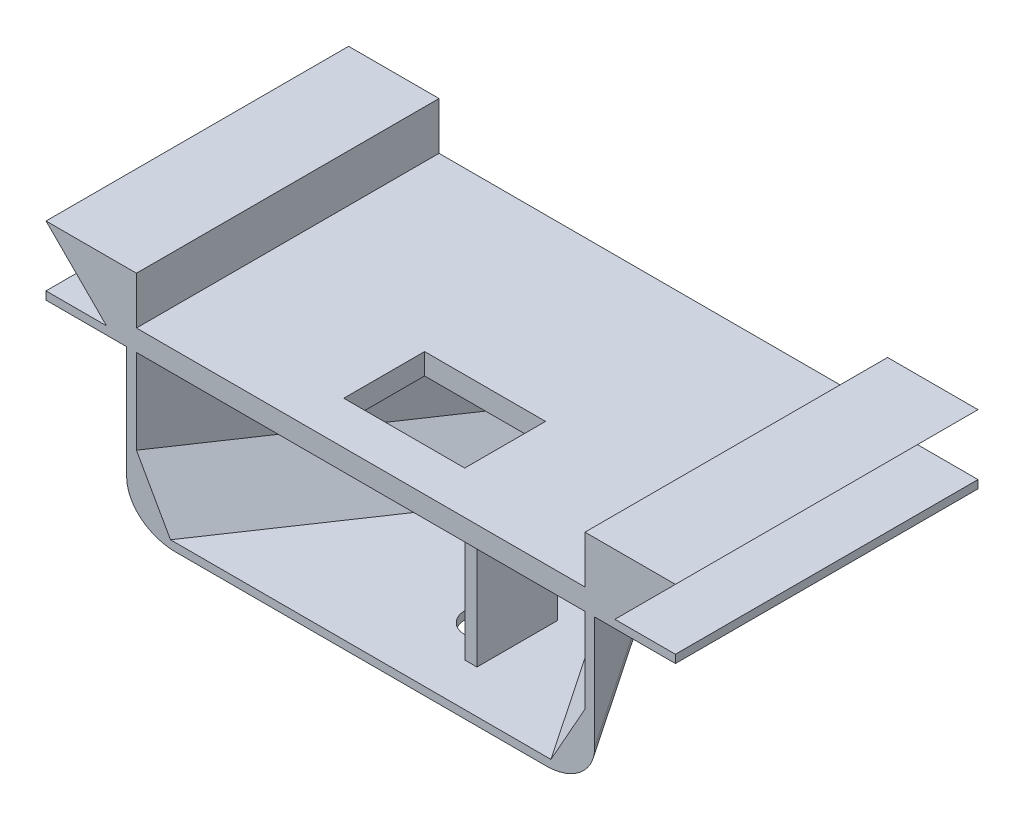
SolidWorks part; units mm, degrees
other "Camera1"
ref_plane "Front Plane" through (0, 0, 0) normal (0, 0, 1) x (1, 0, 0)
ref_plane "Top Plane" through (0, 0, 0) normal (0, 1, 0) x (1, 0, 0)
ref_plane "Right Plane" through (0, 0, 0) normal (1, 0, 0) x (0, 0, -1)
sketch "Sketch1" plane through (0, 0, 0) normal (0, 1, 0) x (1, 0, 0)
  line L0 (0, 0) -> (-116, 0)
  line L1 (-116, 0) -> (-75.5008, 60)
  line L2 (-75.5008, 60) -> (-40.5008, 60)
  line L3 (-40.5008, 60) -> (0, 0)
  dimension "D1" = 60
  dimension "D2" = 116
  dimension "D3" = 35
  dimension "D5" = 72.39
  dimension "D6" = 72.3891
extrude "Boss-Extrude1" add sketch "Sketch1" against normal blind 40
shell "Shell1" thickness 2 removed face at (-58, -20, 0)
sketch "Sketch5" plane through (0, 0, -58) normal (0, 0, 1) x (1, 0, 0)
  line L0 (-41.5637, -2) -> (-74.4378, -2) construction
  line L1 (-53.4928, -23) -> (-61.9928, -23)
  line L2 (-53.4928, -23) -> (-53.4928, -14.5)
  line L3 (-53.4928, -14.5) -> (-61.9928, -14.5)
  line L4 (-61.9928, -23) -> (-61.9928, -14.5)
  line L5 (-74.4378, -38) -> (-74.4378, -2) construction
  line L7 (-41.5637, -38) -> (-41.5637, -2) construction
  dimension "D1" = 12.445
  dimension "D2" = 8.5
  dimension "D3" = 12.5
  dimension "D4" = 11.929
extrude "Cut-Extrude5" cut sketch "Sketch5" against normal blind 6
chamfer "Chamfer3" distance 15 angle 25 2 edges at (-94.0124, -38, -29) (-21.9884, -38, -29) first distance on face at (-94.0124, -20, -29) first distance on face at (-21.9884, -20, -29)
fillet "Fillet1" radius 10 2 edges at (-20.2504, -40, -30) (-95.7504, -40, -30)
fillet "Fillet2" radius 5 5 edges at (-40.5008, -15, -60) (-44.0345, -37.0711, -60) (-75.5008, -15, -60) (-71.9671, -37.0711, -60) (-58.0008, -40, -60)
sketch "Sketch12" plane through (0, -40, 0) normal (0, -1, 0) x (-1, 0, 0)
  circle A0 centre (48.251, 21.2853) radius 5.2
sketch "Sketch13" plane through (0, -2, 0) normal (0, -1, 0) x (1, 0, 0)
  line L1 (-39.8423, -30.6584) -> (-42.8423, -30.6584)
  line L2 (-39.8423, -30.6584) -> (-39.8423, -10.6584)
  line L3 (-39.8423, -10.6584) -> (-42.8423, -10.6584)
  line L4 (-42.8423, -30.6584) -> (-42.8423, -10.6584)
  dimension "D1" = 3
extrude "Boss-Extrude3" add sketch "Sketch13" along normal blind 36
extrude "Cut-Extrude12" cut sketch "Sketch12" against normal blind 9
sketch "Sketch15" plane through (0, 0, 0) normal (0, 1, 0) x (1, 0, 0)
  line L8 (-136, 75) -> (20, 75)
  line L9 (20, 0) -> (20, 75)
  line L10 (20, 0) -> (-136, 0)
  line L11 (-136, 0) -> (-136, 75)
extrude "Boss-Extrude7" add sketch "Sketch15" along normal blind 15
sketch "Sketch16" plane through (0, 0, 0) normal (0, 0, 1) x (1, 0, 0)
  line L8 (20, 15) -> (20, 0)
  line L9 (20, 0) -> (5, 0)
  line L10 (0, 0) -> (20, 0) construction
  line L11 (5, 0) -> (20, 15)
  dimension "D1" = 15
extrude "Cut-Extrude14" cut sketch "Sketch16" against normal blind 75
sketch "Sketch17" plane through (0, 0, 0) normal (0, 0, 1) x (1, 0, 0)
  line L0 (-136, 15) -> (-136, 0)
  line L1 (-136, 0) -> (-121, 0)
  line L2 (-136, 0) -> (-116, 0) construction
  line L3 (-121, 0) -> (-136, 15)
extrude "Cut-Extrude15" cut sketch "Sketch17" against normal blind 75
sketch "Sketch18" plane through (0, 0, 0) normal (0, -1, 0) x (1, 0, 0)
  line L0 (-116, 0) -> (-121, 0)
  line L1 (-121, 0) -> (-136.0045, 0)
  line L2 (-136.0045, 0) -> (-136.0045, -75)
  line L3 (-136.0045, -75) -> (-121, -75)
  line L5 (20.0045, -75) -> (20.0045, 0)
  line L6 (20.0045, 0) -> (-116, 0)
  line L7 (20.0045, -75) -> (5, -75)
  line L8 (-121, -75) -> (5, -75)
  dimension "D1" = 75
extrude "Boss-Extrude8" add sketch "Sketch18" along normal blind 2 contours L8 L7 L5 L6 L0 L1 L2 L3
sketch "Sketch20" plane through (0, -2, 0) normal (0, -1, 0) x (-1, 0, 0)
  line L1 (42.8423, 30.6584) -> (72.8207, 30.6584)
  line L2 (42.8423, 30.6584) -> (42.8423, 10.6218)
  line L3 (42.8423, 10.6218) -> (72.8207, 10.6218)
  line L4 (72.8207, 30.6584) -> (72.8207, 10.6218)
extrude "Cut-Extrude17" cut sketch "Sketch20" against normal blind 39 contours L2 L1 L4 L3
sketch "Sketch21" plane through (0, 0, 0) normal (0, 0, 1) x (1, 0, 0)
  line L6 (-136, 15) -> (20, 15) construction
  line L7 (-2.413, 15) -> (-113.583, 15)
  line L9 (-2.413, 15) -> (-113.583, 15)
  line L11 (-2.413, 15) -> (-2.413, 3.2309)
  line L12 (-2.413, 3.2309) -> (-113.583, 3.2309)
  line L13 (-113.583, 15) -> (-113.583, 3.2309)
extrude "Cut-Extrude18" cut sketch "Sketch21" against normal blind 80 contours L11 L9 L13 L12
